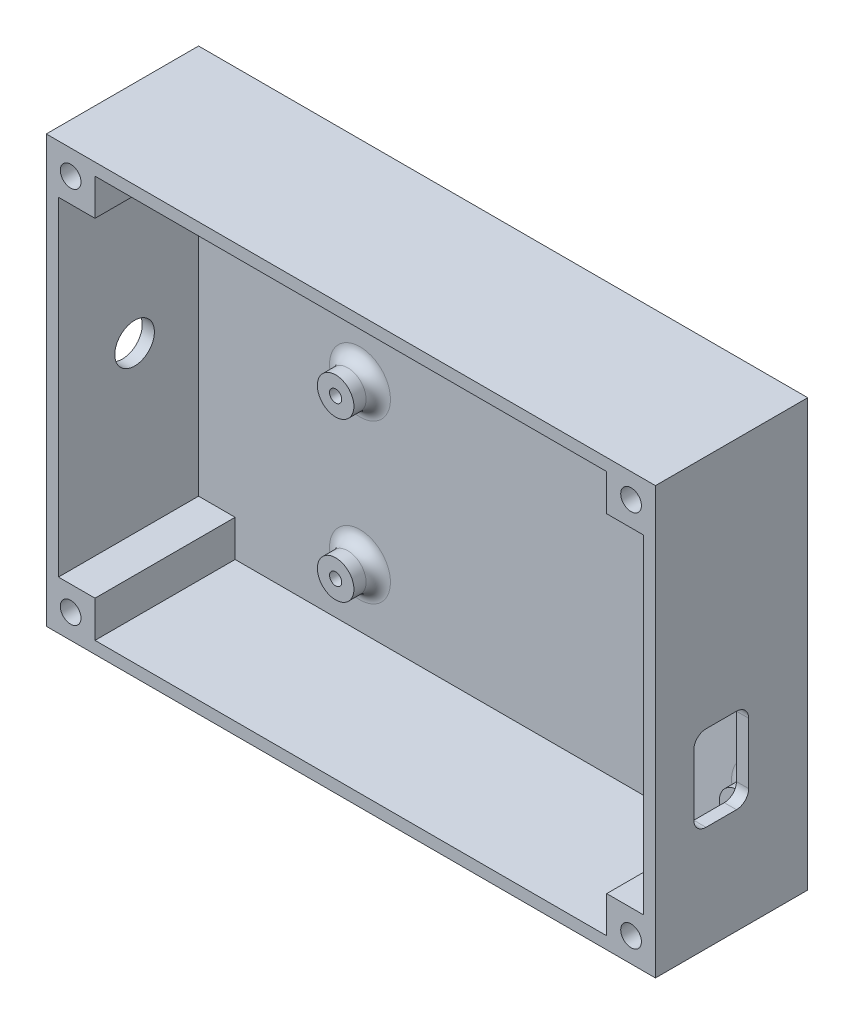
SolidWorks part; units mm, degrees
material "PET"
ref_plane "Ebene vorne" through (0, 0, 0) normal (0, 0, 1) x (1, 0, 0)
ref_plane "Ebene oben" through (0, 0, 0) normal (0, 1, 0) x (1, 0, 0)
ref_plane "Ebene rechts" through (0, 0, 0) normal (1, 0, 0) x (0, 0, -1)
sketch "Skizze1" plane through (0, 0, 0) normal (0, 0, 1) x (1, 0, 0)
  line L1 (0, 0) -> (-100, 0)
  line L2 (0, 0) -> (0, -70)
  line L3 (0, -70) -> (-100, -70)
  line L4 (-100, 0) -> (-100, -70)
  dimension "D1" = 100
  dimension "D2" = 70
extrude "Aufsatz-Linear austragen1" add sketch "Skizze1" along normal blind 25
shell "Wandung1" thickness 2 removed face at (-50, -35, 25)
sketch "Skizze2" plane through (0, 0, 2) normal (0, 0, 1) x (1, 0, 0)
  line L1 (-98, -2) -> (-92, -2)
  line L2 (-98, -2) -> (-98, -8)
  line L3 (-98, -8) -> (-92, -8)
  line L4 (-92, -2) -> (-92, -8)
  line L5 (-2, -2) -> (-8, -2)
  line L6 (-2, -2) -> (-2, -8)
  line L7 (-2, -8) -> (-8, -8)
  line L8 (-8, -2) -> (-8, -8)
  line L9 (-2, -68) -> (-8, -68)
  line L10 (-2, -68) -> (-2, -62)
  line L11 (-2, -62) -> (-8, -62)
  line L12 (-8, -68) -> (-8, -62)
  line L13 (-98, -68) -> (-92, -68)
  line L14 (-98, -68) -> (-98, -62)
  line L15 (-98, -62) -> (-92, -62)
  line L16 (-92, -68) -> (-92, -62)
  dimension "D1" = 6
  dimension "D2" = 6
extrude "Aufsatz-Linear austragen2" add sketch "Skizze2" along normal up to surface (23 mm away) up to face at (-50, -35, 25)
sketch "Skizze5" plane through (0, 0, 2) normal (0, 0, 1) x (1, 0, 0)
  line L1 (-9, -3) -> (-85.2, -3)
  line L2 (-9, -3) -> (-9, -24.5)
  line L3 (-9, -24.5) -> (-85.2, -24.5)
  line L4 (-85.2, -3) -> (-85.2, -24.5)
  line L5 (-8, -2) -> (-92, -2) construction
  line L6 (-8, -2) -> (-8, -8) construction
  dimension "D1" = 76.2
  dimension "D2" = 21.5
  dimension "D3" = 1
  dimension "D4" = 1
extrude "Schnitt-Linear austragen3" cut sketch "Skizze5" against normal blind 0.5
sketch "Skizze6" plane through (0, 0, 2) normal (0, 0, 1) x (1, 0, 0)
  line L0 (-2, -62) -> (-2, -8) construction
  line L1 (-2, -62) -> (-8, -62) construction
  circle A0 centre (-5.5, -58.5) radius 3
  circle A1 centre (-5.5, -32.5) radius 3
  circle A2 centre (-71.5, -32.5) radius 3
  circle A3 centre (-71.5, -58.5) radius 3
  dimension "D5" = 6
  dimension "D6" = 3.5
  dimension "D1" = 26
  dimension "D2" = 26
  dimension "D3" = 66
  dimension "D4" = 66
  dimension "D7" = 3.5
  dimension "D8" = 3.5
  dimension "D9" = 3.5
extrude "Aufsatz-Linear austragen7" add sketch "Skizze6" along normal blind 4 contours A2 | A3 | A0 | A1
hole_wizard "Ø2.0 (2) Durchmesser Bohrung1" positions "Skizze7" profile "Skizze8" hole size "Ø2.0" standard "ANSI Metric"
sketch "Skizze7" plane through (0, 0, 6) normal (0, 0, 1) x (1, 0, 0)
  circle A0 centre (-71.5, -32.5) radius 3 construction
  circle A2 centre (-71.5, -58.5) radius 3 construction
  circle A3 centre (-5.5, -58.5) radius 3 construction
  circle A4 centre (-5.5, -32.5) radius 3 construction
  point P0 (-71.5, -32.5)
  point P3 (-71.5, -58.5)
  point P5 (-5.5, -32.5)
  point P7 (-5.5, -58.5)
sketch "Skizze8" plane through (-71.5, -32.5, 6) normal (1, 0, 0) x (0, -1, 0)
  line L0 (0, 0) -> (0, 4.6009)
  line L1 (0, 4.6009) -> (1, 4)
  line L2 (1, 4) -> (1, 0)
  line L5 (1, 0) -> (0, 0)
  line L10 (0, 4.6009) -> (-1, 4) construction
  line L11 (0, -6.35) -> (0, 107.95) construction
  dimension "Bohrerdurchmesser" = 2
  dimension "Bohrungstiefe" = 4
  dimension "Spitzenwinkel" = 118
sketch "Skizze9" plane through (0, 0, 6) normal (0, 0, 1) x (1, 0, 0)
  line L0 (-5.5, -32.9484) -> (-5.5, -58.5) construction
sketch "Skizze3" plane through (0, 0, 0) normal (1, 0, 0) x (0, 0, -1)
  line L0 (-6, -32.9484) -> (-6, -58.5) construction
  line L1 (-18.7, -38.7242) -> (-9.7, -38.7242)
  line L2 (-18.7, -38.7242) -> (-18.7, -52.7242)
  line L3 (-18.7, -52.7242) -> (-9.7, -52.7242)
  line L4 (-9.7, -38.7242) -> (-9.7, -52.7242)
  line L5 (-18.7, -38.7242) -> (-9.7, -52.7242) construction
  line L6 (-18.7, -52.7242) -> (-9.7, -38.7242) construction
  point P0 (-14.2, -45.7242)
  dimension "D1" = 8.2
  dimension "D2" = 14
  dimension "D3" = 9
extrude "Schnitt-Linear austragen USB" cut sketch "Skizze3" against normal up to next
sketch "Skizze4" plane through (-100, 0, 0) normal (-1, 0, 0) x (0, 0, 1)
  line L0 (25, 0) -> (0, -70) construction
  circle A0 centre (12.5, -35) radius 3.25
  dimension "D1" = 6.5
extrude "Schnitt-Linear austragen Antenne" cut sketch "Skizze4" against normal up to next contours A0
hole_wizard "Ø3.4 (3.4) Durchmesser Bohrung1" positions "Skizze11" profile "Skizze12" hole size "Ø3.4" standard "ANSI Metric"
sketch "Skizze11" plane through (0, 0, 25) normal (0, 0, 1) x (1, 0, 0)
  line L0 (0, 0) -> (-100, 0) construction
  line L1 (-100, 0) -> (-100, -70) construction
  line L2 (0, -70) -> (0, 0) construction
  line L3 (-100, -70) -> (0, -70) construction
  point P0 (-96, -4)
  point P2 (-4, -4)
  point P4 (-4, -66)
  point P6 (-96, -66)
  dimension "D1" = 4
  dimension "D2" = 4
  dimension "D3" = 4
  dimension "D4" = 4
  dimension "D5" = 4
  dimension "D6" = 4
  dimension "D7" = 4
  dimension "D8" = 4
sketch "Skizze12" plane through (-96, -4, 25) normal (1, 0, 0) x (0, -1, 0)
  line L0 (0, 0) -> (0, 7.0215)
  line L1 (0, 7.0215) -> (1.7, 6)
  line L2 (1.7, 6) -> (1.7, 0)
  line L5 (1.7, 0) -> (0, 0)
  line L10 (0, 7.0215) -> (-1.7, 6) construction
  line L11 (0, -6.35) -> (0, 107.95) construction
  dimension "Bohrerdurchmesser" = 3.4
  dimension "Bohrungstiefe" = 6
  dimension "Spitzenwinkel" = 118
fillet "Verrundung1" radius 2 4 edges at (-1, -38.7242, 9.7) (-1, -38.7242, 18.7) (-1, -52.7242, 18.7) (-1, -52.7242, 9.7)
fillet "Verrundung2" radius 2 4 edges at (-8.5, -58.5, 2) (-74.5, -32.5, 2) (-8.5, -32.5, 2) (-74.5, -58.5, 2)
